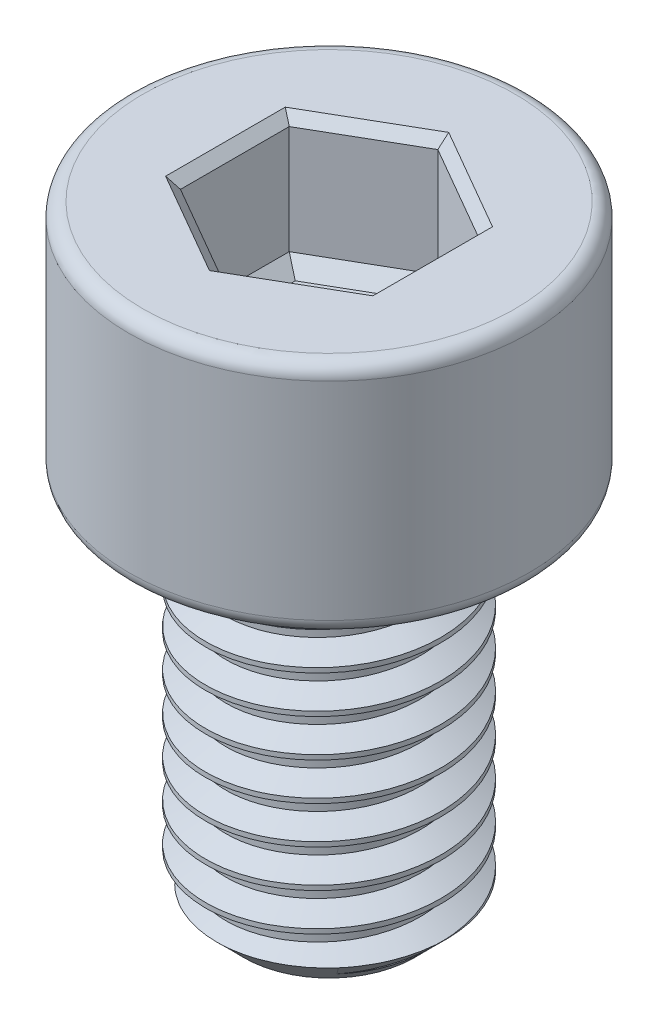
SolidWorks part; units mm, degrees
material "AISI Type A2 Tool Steel"
ref_plane "Front Plane" through (0, 0, 0) normal (0, 0, 1) x (1, 0, 0)
ref_plane "Top Plane" through (0, 0, 0) normal (0, 1, 0) x (1, 0, 0)
ref_plane "Right Plane" through (0, 0, 0) normal (1, 0, 0) x (0, 0, -1)
sketch "Sketch1" plane through (0, 0, 0) normal (0, 1, 0) x (1, 0, 0)
  circle A0 centre (0, 0) radius 2.5
  dimension "D1" = 5
extrude "Boss-Extrude1" add sketch "Sketch1" along normal blind 8
thread "Thread1" pitch 0.8 method cut profile "Thread Profile1" start angle 0, offset 1, length 0, pitch 0.8, diameter 5
ref_plane "Plane1" through (-2.5, 9, 0) normal (0, 0, 1) x (-1, 0, 0)
sketch "Thread Profile1" plane through (-2.5, 9, 0) normal (0, 0, 1) x (-1, 0, 0)
  line L0 (0, 0) -> (0, 0.8) construction
  line L11 (0, 0) -> (0, 0.7)
  line L12 (0, 0.7) -> (-0.433, 0.45)
  line L13 (-0.433, 0.45) -> (-0.433, 0.25)
  line L15 (-0.433, 0.25) -> (0, 0)
  line L17 (-0.433, 0.35) -> (0, 0.35) construction
  point P2 (0, 0)
  dimension "Pitch" = 0.8
  dimension "Profile_Angle" = 60
  dimension "Profile_Land" = 0.2
  dimension "Profile_Height" = 0.433
sketch "Sketch5" plane through (0, 8, 0) normal (0, 1, 0) x (1, 0, 0)
  circle A0 centre (0, 0) radius 4.25
  dimension "D1" = 8.5
extrude "Boss-Extrude2" add sketch "Sketch5" along normal blind 5
fillet "Fillet1" radius 0.3 2 edges at (0, 8, 4.25) (0, 13, 4.25)
sketch "Sketch6" plane through (0, 0, 0) normal (0, 0, 1) x (1, 0, 0)
  line L0 (0, 0) -> (0, 0.2882) construction
  line L1 (0, 0) -> (2.51, 0) construction
  line L2 (2.51, 0) -> (2.51, 0.7)
  line L3 (2.51, 0.7) -> (1.81, 0)
  line L4 (1.81, 0) -> (2.51, 0)
  dimension "D1" = 45
  dimension "D2" = 0.7
  dimension "D3" = 2.51
revolve "Cut-Revolve1" cut sketch "Sketch6" angle 360 about L0
sketch "Sketch7" plane through (0, 13, 0) normal (0, 1, 0) x (1, 0, 0)
  line L1 (0, 2.3094) -> (-2, 1.1547)
  line L2 (-2, 1.1547) -> (-2, -1.1547)
  line L3 (-2, -1.1547) -> (0, -2.3094)
  line L4 (0, -2.3094) -> (2, -1.1547)
  line L5 (2, -1.1547) -> (2, 1.1547)
  line L6 (2, 1.1547) -> (0, 2.3094)
  circle A0 centre (0, 0) radius 2 construction
  dimension "D1" = 4
extrude "Cut-Extrude1" cut sketch "Sketch7" against normal blind 2.5
chamfer "Chamfer1" distance 0.2 angle 45 6 edges at (-2, 13, 0) (-1, 13, 1.7321) (1, 13, 1.7321) (2, 13, 0) (1, 13, -1.7321) (-1, 13, -1.7321)
sketch "Sketch8" plane through (0, 10.5, 0) normal (0, 1, 0) x (1, 0, 0)
  line L1 (0, 2.3094) -> (-2, 1.1547)
  line L2 (-2, 1.1547) -> (-2, -1.1547)
  line L3 (-2, -1.1547) -> (0, -2.3094)
  line L4 (0, -2.3094) -> (2, -1.1547)
  line L5 (2, -1.1547) -> (2, 1.1547)
  line L6 (2, 1.1547) -> (0, 2.3094)
  circle A0 centre (0, 0) radius 2 construction
extrude "Cut-Extrude2" cut sketch "Sketch8" against normal blind 0.3 draft 45
